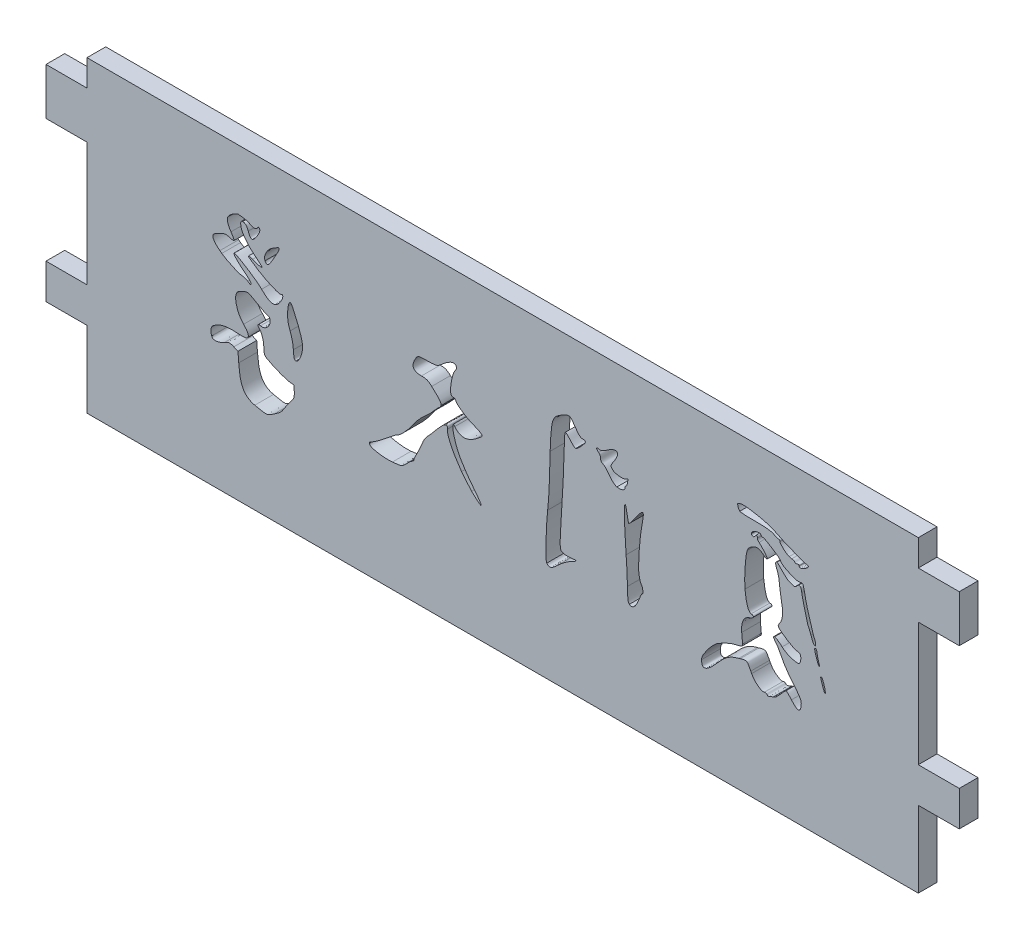
SolidWorks part; units mm, degrees
ref_plane "前视基准面" through (0, 0, 0) normal (0, 0, 1) x (1, 0, 0)
ref_plane "上视基准面" through (0, 0, 0) normal (0, 1, 0) x (1, 0, 0)
ref_plane "右视基准面" through (0, 0, 0) normal (1, 0, 0) x (0, 0, -1)
sketch "草图1" plane through (0, 0, 0) normal (0, 0, 1) x (1, 0, 0)
  line L0 (0, 0) -> (0, 38.8053) construction
  line L11 (0, 0) -> (-51.2518, 0) construction
  line L12 (39, 4) -> (-39, 4)
  line L13 (-39, 4) -> (-39, 0)
  line L14 (-39, 0) -> (-35.5, 0)
  line L15 (-35.5, 0) -> (-35.5, -13.55) construction
  line L16 (-35.5, -13.55) -> (35.5, -13.55)
  line L17 (35.5, 0) -> (35.5, -13.55) construction
  line L18 (39, 0) -> (35.5, 0)
  line L19 (39, 4) -> (39, 0)
  line L20 (-35.5, -10.55) -> (-39, -10.55)
  line L21 (-39, -10.55) -> (-39, -13.55)
  line L22 (-39, -13.55) -> (-35.5, -13.55)
  line L23 (-35.5, 0) -> (-35.5, -10.55)
  line L24 (39, -13.55) -> (35.5, -13.55)
  line L25 (39, -10.55) -> (39, -13.55)
  line L26 (35.5, -10.55) -> (39, -10.55)
  line L27 (35.5, 0) -> (35.5, -10.55)
  line L28 (-39, 2) -> (-43.2943, 2) construction
  point P6 (-37.25, 0)
  point P12 (0, -13.55)
  point P15 (0, 4)
  point P23 (0, 0)
  point P24 (0, 0)
  point P25 (0, 0)
  dimension "D1" = 3.5
  dimension "D2" = 4
  dimension "D3" = 71
  dimension "D4" = 12.55
  dimension "D5" = 3
extrude "主体" add sketch "草图1" along normal blind 1.6
ref_plane "旋转轴所在面" through (0, 0, 0.8) normal (0, 0, -1) x (-1, 0, 0)
sketch "旋转轴示意" plane through (0, 0, 0.8) normal (0, 0, -1) x (-1, 0, 0)
  line L0 (-39, 2) -> (-50.9061, 2) construction
  line L1 (-39, 0) -> (-39, 4) construction
sketch "草图3" plane through (0, 0, 0) normal (0, 0, -1) x (-1, 0, 0)
  line L0 (-35.5, 4) -> (-35.5, 6.25)
  line L1 (-39, 4) -> (39, 4) construction
  line L2 (-35.5, 6.25) -> (35.5, 6.25)
  line L3 (35.5, 6.25) -> (35.5, 4)
  line L4 (35.5, 4) -> (-35.5, 4)
  line L5 (-35.5, -10.55) -> (-35.5, 0) construction
  line L6 (35.5, 0) -> (35.5, -10.55) construction
  line L7 (-35.5, -20.05) -> (-35.5, -13.55)
  line L8 (-35.5, -13.55) -> (35.5, -13.55)
  line L9 (35.5, -13.55) -> (35.5, -20.05)
  line L10 (35.5, -20.05) -> (-35.5, -20.05)
  line L11 (39, -13.55) -> (-39, -13.55) construction
  dimension "D1" = 2.25
  dimension "D2" = 6.5
extrude "结构补强" add sketch "草图3" against normal up to surface (1.6 mm away) up to face at (0, -5.1083, 1.6)
sketch "草图4" plane through (0, 0, 0) normal (0, 0, -1) x (-1, 0, 0)
  line L0 (-39, -12.05) -> (39, -12.05) construction
  line L1 (-39, -13.55) -> (-39, -10.55) construction
  line L2 (39, -10.55) -> (39, -13.55) construction
  text T0 "  厦门大学" font "钟齐志莽行书" height 12.5
extrude "切除-拉伸2" cut sketch "草图4" along normal through all and the other way through all body kept at (39, 4, 0)
